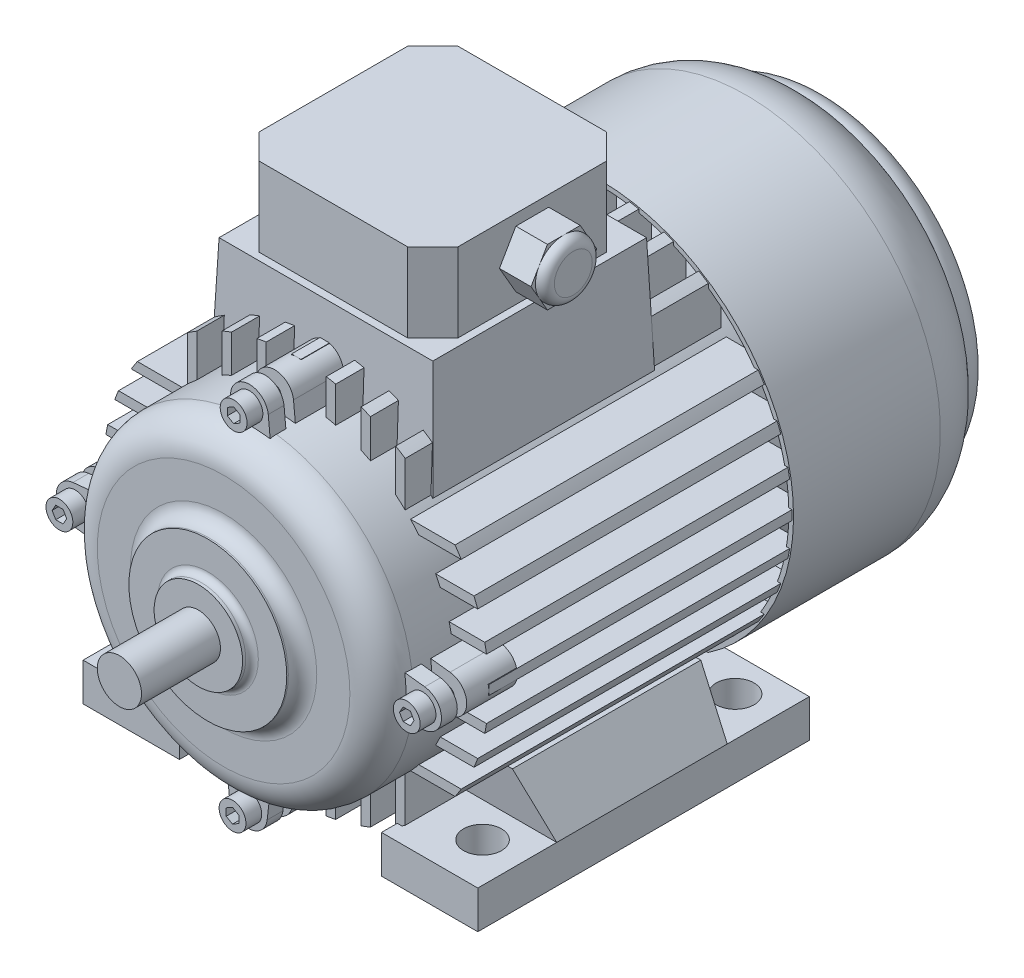
SolidWorks part; units mm, degrees
material "Cast Alloy Steel"
ref_plane "Front Plane" through (0, 0, 0) normal (0, 0, 1) x (1, 0, 0)
ref_plane "Top Plane" through (0, 0, 0) normal (0, 1, 0) x (1, 0, 0)
ref_plane "Right Plane" through (0, 0, 0) normal (1, 0, 0) x (0, 0, -1)
sketch "Sketch1" plane through (0, 0, 0) normal (1, 0, 0) x (0, 0, -1)
  line L0 (0, 7) -> (0, 14)
  line L1 (0, 14) -> (1, 14)
  line L2 (3, 16) -> (3, 25)
  line L3 (3, 25) -> (3.5, 25)
  line L4 (8, 29.5) -> (8, 40)
  line L5 (18, 50) -> (142, 50)
  line L6 (152, 40) -> (152, 0)
  line L7 (152, 0) -> (25, 0)
  line L8 (0, 7) -> (25, 7)
  line L9 (25, 7) -> (25, 0)
  line L10 (0, 0) -> (23.2851, 0) construction
  arc A0 (8, 40) -> (18, 50) centre (18, 40) cw
  arc A1 (142, 50) -> (152, 40) centre (142, 40) cw
  arc A2 (3.5, 25) -> (8, 29.5) centre (3.5, 29.5) ccw
  arc A3 (1, 14) -> (3, 16) centre (1, 16) ccw
  point P21 (3, 14)
  dimension "D8" = 10
  dimension "D9" = 10
  dimension "D11" = 4.5
  dimension "D12" = 2
  dimension "D1" = 152
  dimension "D2" = 25
  dimension "D3" = 14
  dimension "D4" = 3
  dimension "D5" = 28
  dimension "D6" = 50
  dimension "D7" = 100
  dimension "D10" = 15
revolve "Revolve1" add sketch "Sketch1" angle 360 about L10
ref_plane "Plane1" through (0, 0, -81) normal (0, 0, -1) x (-1, 0, 0)
sketch "Sketch2" plane through (0, 0, -81) normal (0, 0, -1) x (-1, 0, 0)
  line L0 (-61, 0) -> (-50, 0) construction
  line L1 (-60, 11) -> (-48.775, 11) construction
  line L2 (-56.8946, 22) -> (-44.8999, 22) construction
  line L3 (-51.303, 33) -> (-37.5633, 33) construction
  line L4 (-60.9816, -1.5) -> (-49.9775, -1.5)
  line L5 (-60.9816, 1.5) -> (-49.9775, 1.5)
  line L6 (-60.2557, 9.5) -> (-49.0892, 9.5)
  line L7 (-59.7055, 12.5) -> (-48.4123, 12.5)
  line L8 (-57.4522, 20.5) -> (-45.6043, 20.5)
  line L9 (-56.2917, 23.5) -> (-44.1333, 23.5)
  line L10 (-52.2374, 31.5) -> (-38.8298, 31.5)
  line L11 (-50.3066, 34.5) -> (-36.1905, 34.5)
  line L12 (-78.5226, 34.5) -> (61, 34.5) construction
  line L13 (-78.5226, 33) -> (61, 33) construction
  line L14 (-78.5226, 31.5) -> (61, 31.5) construction
  line L15 (-78.5226, 23.5) -> (61, 23.5) construction
  line L16 (-78.5226, 22) -> (61, 22) construction
  line L17 (-78.5226, 20.5) -> (61, 20.5) construction
  line L18 (-78.5226, 12.5) -> (61, 12.5) construction
  line L19 (-78.5226, 11) -> (61, 11) construction
  line L20 (-78.5226, 9.5) -> (61, 9.5) construction
  line L21 (-78.5226, 1.5) -> (61, 1.5) construction
  line L22 (-78.5226, 0) -> (61, 0) construction
  line L23 (-78.5226, -1.5) -> (61, -1.5) construction
  line L24 (0, 0) -> (88.23, 0) construction
  line L25 (-51.303, -33) -> (-37.5633, -33) construction
  line L26 (-56.8946, -22) -> (-44.8999, -22) construction
  line L27 (-60, -11) -> (-48.775, -11) construction
  line L28 (-50.3066, -34.5) -> (-36.1905, -34.5)
  line L29 (-52.2374, -31.5) -> (-38.8298, -31.5)
  line L30 (-56.2917, -23.5) -> (-44.1333, -23.5)
  line L31 (-57.4522, -20.5) -> (-45.6043, -20.5)
  line L32 (-59.7055, -12.5) -> (-48.4123, -12.5)
  line L33 (-60.2557, -9.5) -> (-49.0892, -9.5)
  arc A3 (-60.9816, 1.5) -> (-60.9816, -1.5) centre (0, 0) ccw
  arc A4 (-59.7055, 12.5) -> (-60.2557, 9.5) centre (0, 0) ccw
  arc A5 (-56.2917, 23.5) -> (-57.4522, 20.5) centre (0, 0) ccw
  arc A6 (-50.3066, 34.5) -> (-52.2374, 31.5) centre (0, 0) ccw
  circle A7 centre (0, 0) radius 61 construction
  arc A8 (-48.4123, 12.5) -> (-49.0892, 9.5) centre (0, 0) ccw
  arc A9 (-36.1905, 34.5) -> (-38.8298, 31.5) centre (0, 0) ccw
  arc A10 (-44.1333, 23.5) -> (-45.6043, 20.5) centre (0, 0) ccw
  arc A11 (-49.9775, 1.5) -> (-49.9775, -1.5) centre (0, 0) ccw
  arc A12 (-44.1333, -23.5) -> (-45.6043, -20.5) centre (0, 0) cw
  arc A13 (-36.1905, -34.5) -> (-38.8298, -31.5) centre (0, 0) cw
  arc A14 (-48.4123, -12.5) -> (-49.0892, -9.5) centre (0, 0) cw
  arc A15 (-50.3066, -34.5) -> (-52.2374, -31.5) centre (0, 0) cw
  arc A16 (-56.2917, -23.5) -> (-57.4522, -20.5) centre (0, 0) cw
  arc A17 (-59.7055, -12.5) -> (-60.2557, -9.5) centre (0, 0) cw
  point P5 (0, 0)
  dimension "D13" = 122
  dimension "D1" = 11
  dimension "D2" = 11
  dimension "D3" = 11
  dimension "D5" = 1.5
  dimension "D6" = 1.5
  dimension "D7" = 1.5
  dimension "D8" = 1.5
  dimension "D9" = 1.5
  dimension "D10" = 1.5
  dimension "D11" = 1.5
  dimension "D12" = 1.5
extrude "Boss-Extrude1" add sketch "Sketch2" along normal mid plane 100
ref_plane "Plane2" through (0, 0, -16) normal (0, 0, 1) x (1, 0, 0)
sketch "Sketch3" plane through (0, 0, -16) normal (0, 0, 1) x (1, 0, 0)
  line L1 (-5.7839, 55.6969) -> (-7.7079, 39.2503)
  line L2 (6.1348, 55.6969) -> (7.7079, 39.2503)
  line L3 (0.1754, 51.4997) -> (0.1754, 54.9997) construction
  circle A0 centre (0, 0) radius 40 construction
  arc A1 (7.7079, 39.2503) -> (-7.7079, 39.2503) centre (0, 0) ccw
  arc A2 (6.1348, 55.6969) -> (-5.7839, 55.6969) centre (0.1754, 54.9997) ccw
  circle A3 centre (0, 0) radius 50 construction
  arc A4 (6.7231, 49.5459) -> (4.7061, 49.778) centre (0, 0) ccw
  dimension "D2" = 12
  dimension "D1" = 55
extrude "Boss-Extrude2" add sketch "Sketch3" against normal blind 5
sketch "Sketch4" plane through (0, 0, -16) normal (0, 0, 1) x (1, 0, 0)
  circle A0 centre (0.1754, 54.9997) radius 4.25
  dimension "D1" = 8.5
extrude "Boss-Extrude3" add sketch "Sketch4" along normal blind 5
sketch "Sketch5" plane through (0, 0, -11) normal (0, 0, 1) x (1, 0, 0)
  line L1 (0.1754, 57.3091) -> (-1.8246, 56.1544)
  line L2 (-1.8246, 56.1544) -> (-1.8246, 53.845)
  line L3 (-1.8246, 53.845) -> (0.1754, 52.6903)
  line L4 (0.1754, 52.6903) -> (2.1754, 53.845)
  line L5 (2.1754, 53.845) -> (2.1754, 56.1544)
  line L6 (2.1754, 56.1544) -> (0.1754, 57.3091)
  circle A0 centre (0.1754, 54.9997) radius 2 construction
  dimension "D1" = 4
extrude "Cut-Extrude1" cut sketch "Sketch5" against normal blind 4
sketch "Sketch6" plane through (0, 0, -21) normal (0, 0, -1) x (-1, 0, 0)
  circle A0 centre (-0.1754, 54.9997) radius 2
  dimension "D1" = 4
extrude "Boss-Extrude4" add sketch "Sketch6" along normal blind 3
sketch "Sketch8" plane through (0, 0, -24) normal (0, 0, -1) x (-1, 0, 0)
  line L0 (-6.1348, 55.6969) -> (-6.7231, 49.5459) construction
  line L1 (-6.1348, 55.6969) -> (-6.7231, 49.5459)
  line L2 (5.7839, 55.6969) -> (6.5, 49.5757) construction
  line L3 (5.7839, 55.6969) -> (6.5, 49.5757)
  arc A0 (5.7839, 55.6969) -> (-6.1348, 55.6969) centre (-0.1754, 54.9997) ccw construction
  arc A1 (5.7839, 55.6969) -> (-6.1348, 55.6969) centre (-0.1754, 54.9997) ccw
  circle A2 centre (0, 0) radius 50 construction
  arc A3 (6.5, 49.5757) -> (-6.7231, 49.5459) centre (0, 0) ccw
extrude "Boss-Extrude6" add sketch "Sketch8" along normal blind 16
pattern_circular "CirPattern1" count 4 over 360 about axis through (0, 0, 0) along (0, 0, 1) of "Boss-Extrude1", "Boss-Extrude2", "Boss-Extrude3", "Cut-Extrude1", "Boss-Extrude4", "Boss-Extrude6"
sketch "Sketch9" plane through (0, 0, 0) normal (0, 1, 0) x (1, 0, 0)
  line L0 (60, 127) -> (60, 173.4982)
  line L1 (42.5, 196.3274) -> (0, 196.3274)
  line L2 (0, 196.3274) -> (0, 0) construction
  line L3 (61.5, 127) -> (61.5, 173.4982)
  line L4 (42.0396, 197.8274) -> (0, 197.8274)
  line L5 (0, 197.8274) -> (0, 196.3274)
  line L6 (60, 127) -> (61.5, 127)
  arc A0 (60, 173.4982) -> (50.2115, 190.6948) centre (40, 173.4982) ccw
  arc A1 (50.2115, 190.6948) -> (42.5, 196.3274) centre (45.4806, 192.313) ccw
  arc A2 (61.5, 173.4982) -> (51.9154, 191.3944) centre (40, 173.4982) ccw
  arc A3 (51.9154, 191.3944) -> (42.0396, 197.8274) centre (45.4806, 192.313) ccw
  dimension "D5" = 5
  dimension "D6" = 20
  dimension "D1" = 127
  dimension "D2" = 190.6948
  dimension "D3" = 60
  dimension "D4" = 42.5
  dimension "D7" = 1.5
revolve "Revolve2" add sketch "Sketch9" angle 360 about L2
sketch "Sketch10" plane through (0, 0, -197.8274) normal (0, 0, -1) x (-1, 0, 0)
  line L1 (-3.75, -3.75) -> (3.75, -3.75)
  line L2 (-3.75, -3.75) -> (-3.75, 3.75)
  line L3 (-3.75, 3.75) -> (3.75, 3.75)
  line L4 (3.75, -3.75) -> (3.75, 3.75)
  line L5 (-3.75, -3.75) -> (3.75, 3.75) construction
  line L6 (-3.75, 3.75) -> (3.75, -3.75) construction
  point P0 (0, 0)
  dimension "D1" = 7.5
extrude "Cut-Extrude2" cut sketch "Sketch10" against normal blind 2
pattern_linear "LPattern1" count 4 spacing 10 along (1, 0, 0) count 4 spacing 10 along (0, 1, 0) skipping (3, 3) of "Cut-Extrude2"
pattern_circular "CirPattern2" count 4 over 360 about axis through (0, 0, -173.4982) along (0, 0, -1) of "LPattern1"
ref_plane "Plane3" through (0, -51, 0) normal (0, 1, 0) x (1, 0, 0)
sketch "Sketch11" plane through (0, -51, 0) normal (0, 1, 0) x (1, 0, 0)
  line L0 (0, 0) -> (0, 198.813) construction
  line L1 (45.4806, 198.813) -> (-45.4806, 198.813) construction
  line L2 (-62.5, 105) -> (-62.5, 51)
  line L3 (32.5, 105) -> (62.5, 105)
  line L4 (32.5, 105) -> (32.5, 51)
  line L5 (32.5, 51) -> (62.5, 51)
  line L6 (62.5, 105) -> (62.5, 51)
  line L7 (-32.5, 51) -> (-62.5, 51)
  line L8 (-32.5, 105) -> (-32.5, 51)
  line L9 (-32.5, 105) -> (-62.5, 105)
  dimension "D1" = 54
  dimension "D2" = 30
  dimension "D3" = 51
  dimension "D4" = 62.5
extrude "Boss-Extrude7" add sketch "Sketch11" along normal blind 16
draft "Draft1" type of draft neutral plane draft angle 35 faces to draft 2 face at (62.5, -43, -78) face at (-62.5, -43, -78) neutral plane through (0, -51, 0) neutral plane normal (0, -1, 0) reverse direction yes parameters "D1"=35
draft "Draft2" type of draft neutral plane draft angle 10 faces to draft 4 face at (41.9962, -43.0841, -105) face at (-41.9962, -43.0841, -105) face at (41.9962, -43.0841, -51) face at (-41.9962, -43.0841, -51) neutral plane through (0, -51, 0) neutral plane normal (0, -1, 0) parameters "D1"=10
sketch "Sketch12" plane through (0, -51, 0) normal (0, 1, 0) x (1, 0, 0)
  line L0 (0, 173.4982) -> (0, 142.8169) construction
  line L1 (32, 131) -> (62.5, 131)
  line L2 (32, 131) -> (32, 104)
  line L3 (32, 104) -> (62.5, 104)
  line L4 (62.5, 131) -> (62.5, 104)
  line L5 (-61.5, 173.4982) -> (61.5, 173.4982) construction
  line L6 (-62.5, 53) -> (-62.5, 26)
  line L7 (32, 53) -> (62.5, 53)
  line L8 (32, 53) -> (32, 26)
  line L9 (32, 26) -> (62.5, 26)
  line L10 (62.5, 53) -> (62.5, 26)
  line L11 (-32, 26) -> (-62.5, 26)
  line L12 (-32, 53) -> (-32, 26)
  line L13 (-32, 53) -> (-62.5, 53)
  line L14 (-62.5, 131) -> (-62.5, 104)
  line L15 (-32, 104) -> (-62.5, 104)
  line L16 (-32, 131) -> (-32, 104)
  line L17 (-32, 131) -> (-62.5, 131)
  dimension "D1" = 27
  dimension "D2" = 30.5
  dimension "D3" = 26
  dimension "D4" = 51
extrude "Boss-Extrude8" add sketch "Sketch12" against normal blind 12
sketch "Sketch13" plane through (0, -51, 0) normal (0, 1, 0) x (1, 0, 0)
  line L0 (-58.5, 104) -> (-58.5, 53)
  line L1 (58.5, 53) -> (58.5, 104)
  line L4 (-62.5, 104) -> (-62.5, 53)
  line L5 (-33.4664, 104) -> (-62.5, 104)
  line L6 (-33.4664, 53) -> (-33.4664, 104)
  line L7 (-62.5, 53) -> (-33.4664, 53)
  line L8 (-62.5, 104) -> (-62.5, 53)
  line L9 (-58.5, 104) -> (-62.5, 104)
  line L11 (-62.5, 53) -> (-58.5, 53)
  line L12 (62.5, 53) -> (62.5, 104)
  line L13 (33.4664, 53) -> (62.5, 53)
  line L14 (33.4664, 104) -> (33.4664, 53)
  line L15 (62.5, 104) -> (33.4664, 104)
  line L16 (62.5, 53) -> (62.5, 104)
  line L17 (58.5, 53) -> (62.5, 53)
  line L19 (62.5, 104) -> (58.5, 104)
  dimension "D1" = 0
  dimension "D2" = 0
  dimension "D3" = 4
extrude "Boss-Extrude9" add sketch "Sketch13" against normal up to surface (12 mm away) up to face at (47.25, -63, -39.5)
sketch "Sketch14" plane through (0, -63, 0) normal (0, -1, 0) x (1, 0, 0)
  circle A0 centre (50, -40) radius 6
  circle A1 centre (-50, -40) radius 6
  circle A2 centre (-50, -120) radius 6
  circle A3 centre (50, -120) radius 6
  dimension "D1" = 80
  dimension "D3" = 100
  dimension "D4" = 50
  dimension "D5" = 12
  dimension "D2" = 40
extrude "Cut-Extrude3" cut sketch "Sketch14" against normal up to surface (12 mm away) up to face at (42.6555, -51, -36)
ref_plane "Plane4" through (0, 31.77, 0) normal (0, 1, 0) x (1, 0, 0)
sketch "Sketch15" plane through (0, 31.77, 0) normal (0, 1, 0) x (1, 0, 0)
  line L0 (0, 173.4982) -> (0, 0) construction
  line L1 (-61.5, 173.4982) -> (61.5, 173.4982) construction
  line L3 (-35.25, 39) -> (35.25, 39)
  line L4 (-35.25, 39) -> (-35.25, 109.5)
  line L5 (-35.25, 109.5) -> (35.25, 109.5)
  line L6 (35.25, 39) -> (35.25, 109.5)
  line L7 (-35.25, 39) -> (35.25, 109.5) construction
  line L8 (-35.25, 109.5) -> (35.25, 39) construction
  point P5 (0, 74.25)
  dimension "D1" = 70.5
  dimension "D2" = 39
extrude "Boss-Extrude10" add sketch "Sketch15" along normal offset from surface 135 draft 2
sketch "Sketch16" plane through (0, 72, 0) normal (0, 1, 0) x (1, 0, 0)
  line L0 (-33.8451, 74.25) -> (33.8451, 74.25) construction
  line L1 (-33.8451, 108.0951) -> (-33.8451, 40.4049) construction
  line L2 (33.8451, 40.4049) -> (33.8451, 108.0951) construction
  line L3 (0, 108.0951) -> (0, 74.25) construction
  line L4 (33.8451, 108.0951) -> (-33.8451, 108.0951) construction
  line L6 (-31.5, 97.75) -> (-23.5, 105.75)
  line L7 (-23.5, 42.75) -> (23.5, 42.75)
  line L8 (-31.5, 50.75) -> (-31.5, 97.75)
  line L9 (-23.5, 105.75) -> (23.5, 105.75)
  line L10 (31.5, 50.75) -> (31.5, 97.75)
  line L11 (-31.5, 42.75) -> (31.5, 105.75) construction
  line L12 (-31.5, 105.75) -> (31.5, 42.75) construction
  line L13 (23.5, 105.75) -> (31.5, 97.75)
  line L14 (23.5, 42.75) -> (31.5, 50.75)
  line L15 (-31.5, 50.75) -> (-23.5, 42.75)
  dimension "D1" = 63
extrude "Boss-Extrude11" add sketch "Sketch16" along normal blind 25
sketch "Sketch17" plane through (31.5, 0, 0) normal (1, 0, 0) x (0, 0, -1)
  line L0 (50.75, 84.5) -> (74.25, 84.5) construction
  line L1 (50.75, 97) -> (50.75, 72) construction
  line L2 (74.25, 84.5) -> (74.25, 97) construction
  line L3 (50.75, 97) -> (97.75, 97) construction
  line L5 (79.4462, 93.5) -> (69.0538, 93.5)
  line L6 (69.0538, 93.5) -> (63.8577, 84.5)
  line L7 (63.8577, 84.5) -> (69.0538, 75.5)
  line L8 (69.0538, 75.5) -> (79.4462, 75.5)
  line L9 (79.4462, 75.5) -> (84.6423, 84.5)
  line L10 (84.6423, 84.5) -> (79.4462, 93.5)
  circle A0 centre (74.25, 84.5) radius 9 construction
  dimension "D1" = 18
extrude "Boss-Extrude12" add sketch "Sketch17" along normal blind 10
sketch "Sketch18" plane through (41.5, 0, 0) normal (1, 0, 0) x (0, 0, -1)
  line L0 (74.25, 93.5) -> (74.25, 75.5) construction
  line L1 (79.4462, 93.5) -> (69.0538, 93.5) construction
  line L2 (69.0538, 75.5) -> (79.4462, 75.5) construction
  circle A0 centre (74.25, 84.5) radius 9
  dimension "D1" = 18
extrude "Boss-Extrude13" add sketch "Sketch18" along normal blind 3
fillet "Fillet1" radius 3 1 edges at (44.5, 84.5, -83.25)
sketch "Sketch21" plane through (0, 0, -25) normal (0, 0, 1) x (1, 0, 0)
  circle A0 centre (0, 0) radius 4
  dimension "D1" = 8
sketch "Sketch22" plane through (0, 0, -25) normal (0, 0, 1) x (1, 0, 0)
  circle A0 centre (0, 0) radius 7
  dimension "D1" = 14
extrude "Boss-Extrude14" add sketch "Sketch22" along normal blind 50
